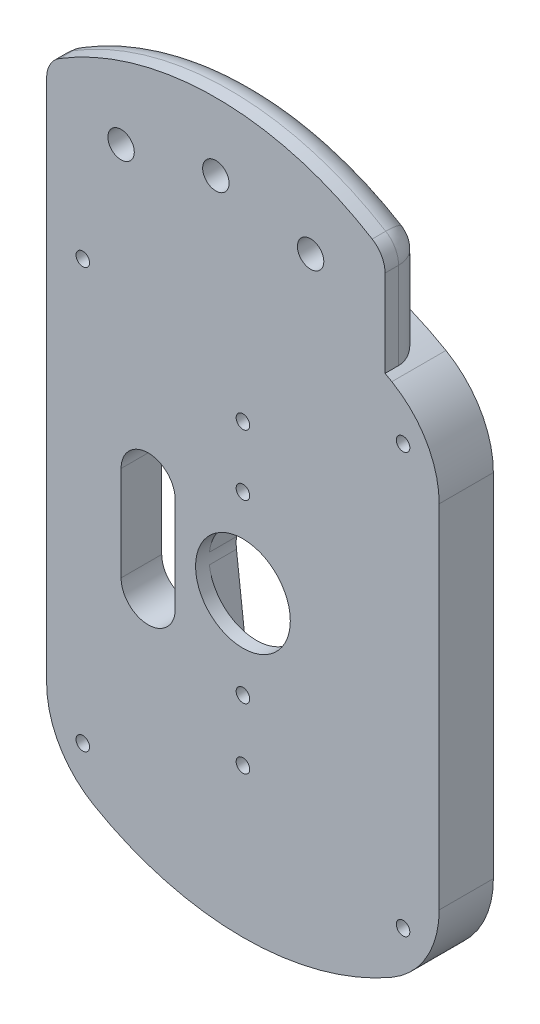
SolidWorks part; units mm, degrees
ref_plane "Спереди" through (0, 0, 0) normal (0, 0, 1) x (1, 0, 0)
ref_plane "Сверху" through (0, 0, 0) normal (0, 1, 0) x (1, 0, 0)
ref_plane "Справа" through (0, 0, 0) normal (1, 0, 0) x (0, 0, -1)
other "Configuration Table"
sketch "Эскиз1" plane through (0, 0, 0) normal (0, 0, 1) x (1, 0, 0)
  line L0 (-6.9532, 0.8077) -> (-3.9733, 26.4615)
  line L1 (3.9733, 26.4615) -> (6.9532, 0.8077)
  line L2 (0, 0) -> (45.5285, 0) construction
  line L3 (3.9733, -26.4615) -> (6.9532, -0.8077)
  line L4 (-6.9532, -0.8077) -> (-3.9733, -26.4615)
  line L5 (25, 25.9808) -> (25, -25.9808)
  line L6 (-25, -25.9808) -> (-25, 25.9808)
  line L7 (0, 0) -> (0, 67.5553) construction
  line L8 (-29, -25.9808) -> (-29, 25.9808)
  line L9 (29, 25.9808) -> (29, -25.9808)
  line L10 (-29, 25.9808) -> (-29, 53.6652)
  line L12 (21, 53.6652) -> (21, 38.6652)
  arc A0 (6.9532, -0.8077) -> (6.9532, 0.8077) centre (0, 0) ccw
  arc A1 (3.9733, 26.4615) -> (-3.9733, 26.4615) centre (0, 26) ccw
  arc A2 (-3.9733, -26.4615) -> (3.9733, -26.4615) centre (0, -26) ccw
  arc A3 (-6.9532, 0.8077) -> (-6.9532, -0.8077) centre (0, 0) ccw
  circle A4 centre (0, 0) radius 7
  circle A5 centre (0, 13) radius 1
  circle A6 centre (0, 22) radius 1
  circle A7 centre (0, -13) radius 1
  circle A8 centre (0, -22) radius 1
  arc A9 (-20, -34.641) -> (20, -34.641) centre (0, 0) ccw
  arc A10 (20, 34.641) -> (-20, 34.641) centre (0, 0) ccw
  arc A11 (-25, -25.9808) -> (-20, -34.641) centre (-15, -25.9808) ccw
  arc A12 (25, -25.9808) -> (20, -34.641) centre (15, -25.9808) cw
  arc A13 (25, 25.9808) -> (20, 34.641) centre (15, 25.9808) ccw
  arc A14 (-25, 25.9808) -> (-20, 34.641) centre (-15, 25.9808) cw
  arc A15 (-29, 25.9808) -> (-22, 38.1051) centre (-15, 25.9808) cw
  arc A16 (22, 38.1051) -> (-22, 38.1051) centre (0, 0) ccw
  arc A17 (29, 25.9808) -> (22, 38.1051) centre (15, 25.9808) ccw
  arc A18 (29, -25.9808) -> (22, -38.1051) centre (15, -25.9808) cw
  arc A19 (-22, -38.1051) -> (22, -38.1051) centre (0, 0) ccw
  arc A20 (-29, -25.9808) -> (-22, -38.1051) centre (-15, -25.9808) ccw
  circle A24 centre (-23.6603, 30.9808) radius 4
  circle A25 centre (23.6603, 30.9808) radius 4
  circle A26 centre (-23.6603, -30.9808) radius 4
  circle A27 centre (23.6603, -30.9808) radius 4
  circle A28 centre (-23.6603, 30.9808) radius 1
  circle A29 centre (23.6603, 30.9808) radius 1
  circle A30 centre (23.6603, -30.9808) radius 1
  circle A31 centre (-23.6603, -30.9808) radius 1
  arc A32 (-29, 53.6652) -> (21, 53.6652) centre (-4, 17.4575) cw
  point P33 (25, 31.225)
  dimension "D1" = 14
  dimension "D2" = 8
  dimension "D6" = 2
  dimension "D7" = 80
  dimension "D9" = 10
  dimension "D11" = 2
  dimension "D3" = 52
  dimension "D4" = 9
  dimension "D5" = 13
  dimension "D8" = 50
  dimension "D12" = 50
  dimension "D13" = 15
  dimension "D10" = 4
extrude "Бобышка-Вытянуть1" add sketch "Эскиз1" along normal blind 6 contours A14 L6 A11 A9 A12 L5 A13 A10 A3 L0 A1 L1 A0 L3 A2 L4 region at (24.0566, 0, 0)
extrude "Бобышка-Вытянуть2" add sketch "Эскиз1<3>" along normal blind 2 contours A4 L1 A1 L0 A6 A5 | A4 L4 A2 L3 A7 A8 region at (0, 16.3649, 0) region at (0, -16.3649, 0)
sketch "Эскиз1<3>" plane through (0, 0, 0) normal (0, 0, 1) x (1, 0, 0) same geometry as "Эскиз1"
extrude "Бобышка-Вытянуть3" add sketch "Эскиз1<4>" along normal blind 8 contours A31 A11 A26 | A31 A11 A26 | A26 A11 L6 A14 A24 A15 L8 A20 | A27 A12 A9 A11 A26 A20 A19 A18 | A30 A12 A27 | A30 A12 A27 | A27 A18 L9 A17 A25 A13 L5 A12 | A29 A13 A25 | A29 A13 A25 | A25 A17 A16 A15 A24 A14 A10 A13 | A28 A14 A24 | A28 A14 A24 region at (27.0355, 0, 0) region at (21.9856, 30.0139, 0) region at (25.0598, 31.7888, 0) region at (25.0598, -31.7888, 0) region at (21.9856, -30.0139, 0) region at (20.8192, 34.785, 0) region at (24.3908, -35.4754, 0) region at (-21.9856, 30.0139, 0) region at (-25.0598, 31.7888, 0) region at (-25.0598, -31.7888, 0) region at (-21.9856, -30.0139, 0) region at (-27.0355, 0, 0)
sketch "Эскиз1<4>" plane through (0, 0, 0) normal (0, 0, 1) x (1, 0, 0) same geometry as "Эскиз1"
sketch "Эскиз2" plane through (0, 0, 6) normal (0, 0, 1) x (1, 0, 0)
  line L0 (0.0013, 0.0008) -> (-44.6361, 0.0008) construction
  line L1 (-13.9987, -6.9992) -> (-13.9987, 7.0008) construction
  line L2 (-17.9987, -6.9992) -> (-17.9987, 7.0008)
  line L3 (-9.9987, -6.9992) -> (-9.9987, 7.0008)
  arc A0 (-17.9987, -6.9992) -> (-9.9987, -6.9992) centre (-13.9987, -6.9992) ccw
  arc A1 (-9.9987, 7.0008) -> (-17.9987, 7.0008) centre (-13.9987, 7.0008) ccw
  point P5 (-13.9987, 0.0008)
  dimension "D3" = 4
  dimension "D1" = 14
  dimension "D2" = 14
extrude "Вырез-Вытянуть1" cut sketch "Эскиз2" against normal through all
extrude "Бобышка-Вытянуть4" add sketch "Эскиз1<5>" along normal blind 6 contours A16 L12 A32 region at (-5.4153, 49.8916, 0)
sketch "Эскиз1<5>" plane through (0, 0, 0) normal (0, 0, 1) x (1, 0, 0) same geometry as "Эскиз1"
fillet "Скругление2" radius 4 5 edges at (-4, 61.4575, 6) (21, 46.1652, 6) (21, 53.6652, 3) (-29, 53.6652, 3) (-29, 39.823, 6)
hole_wizard "Отверстие с зазором M3.51" positions "Эскиз5" profile "Эскиз6" hole size "M3.5" standard "ISO"
sketch "Эскиз5" plane through (0, 0, 6) normal (0, 0, 1) x (1, 0, 0)
  line L0 (-4, 57.4575) -> (-4, 51.4575) construction
  arc A0 (-18, 48.4414) -> (10, 48.4414) centre (-4, 17.4575) cw construction
  arc A1 (17, 51.5016) -> (-25, 51.5016) centre (-4, 17.4575) ccw construction
  point P0 (-18, 48.4414)
  point P2 (-4, 51.4575)
  point P4 (10, 48.4414)
  dimension "D1" = 34
  dimension "D2" = 28
sketch "Эскиз6" plane through (-18, 48.4414, 6) normal (1, 0, 0) x (0, -1, 0)
  line L0 (0, 0) -> (0, 15)
  line L1 (0, 15) -> (1.95, 13.8283)
  line L2 (1.95, 13.8283) -> (1.95, 0)
  line L5 (1.95, 0) -> (0, 0)
  line L10 (0, 15) -> (-1.95, 13.8283) construction
  line L11 (0, -6.35) -> (0, 107.95) construction
  dimension "Диаметр отверстия" = 3.9
  dimension "Глубина отверстия" = 15
  dimension "Угол заточки сверла" = 118
mirror "Зеркальное отражение1" about plane through (0, 0, 0) normal (0, 0, 1) of bodies 108
delete or keep bodies "Тело-Удалить/Сохранить 1" type keep bodies bodies 109
